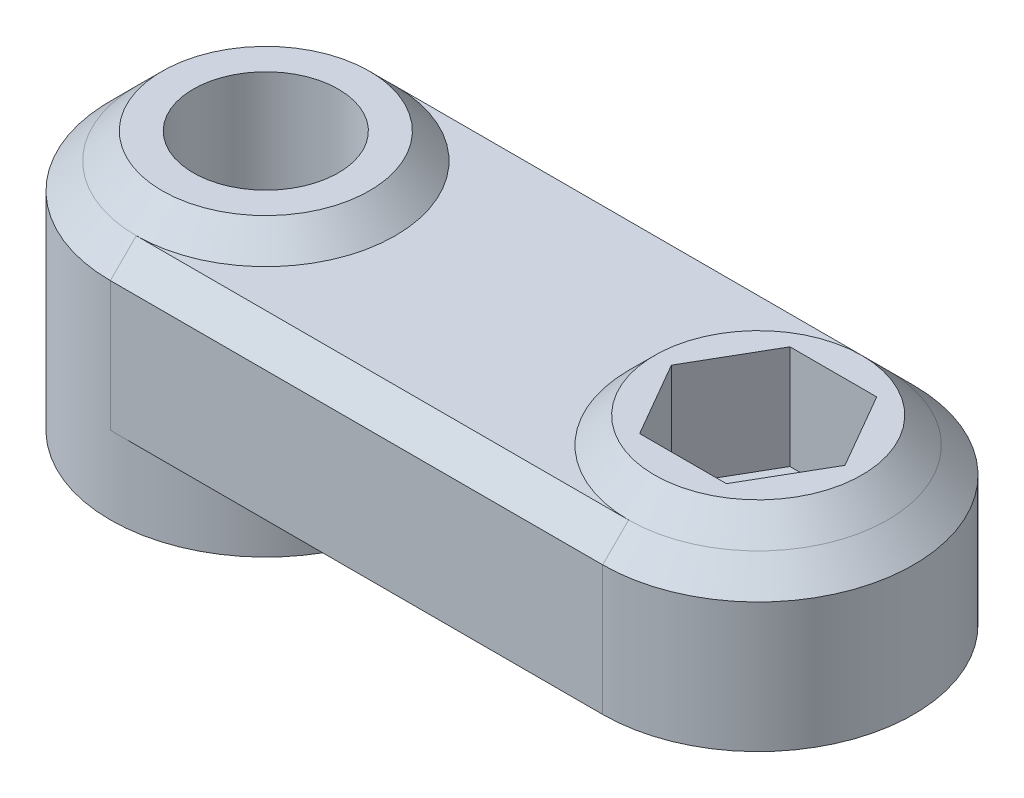
SolidWorks part; units mm, degrees
ref_plane "前视基准面" through (0, 0, 0) normal (0, 0, 1) x (1, 0, 0)
ref_plane "上视基准面" through (0, 0, 0) normal (0, 1, 0) x (1, 0, 0)
ref_plane "右视基准面" through (0, 0, 0) normal (1, 0, 0) x (0, 0, -1)
sketch "草图1" plane through (0, 0, 0) normal (0, 1, 0) x (1, 0, 0)
  line L0 (0, 0) -> (19, 0) construction
  line L1 (0, 6) -> (19, 6)
  line L2 (0, -6) -> (19, -6)
  arc A0 (0, 6) -> (0, -6) centre (0, 0) ccw
  arc A1 (19, -6) -> (19, 6) centre (19, 0) ccw
  point P3 (9.5, 0)
  dimension "D1" = 19
  dimension "D2" = 12
extrude "凸台-拉伸1" add sketch "草图1" along normal blind 10
sketch "草图2" plane through (0, 0, 0) normal (0, 0, 1) x (1, 0, 0)
  line L0 (0, -1.4276) -> (0, 12.6969) construction
  line L1 (0, 10) -> (-2.8, 10)
  line L2 (0, 10) -> (-6, 10) construction
  line L3 (-2.8, 10) -> (-2.8, 5)
  line L4 (-2.8, 5) -> (-1.85, 5)
  line L5 (-1.85, 5) -> (-1.85, 2)
  line L6 (-1.85, 2) -> (-2.8, 2)
  line L7 (-2.8, 2) -> (-2.8, 0)
  line L8 (-6, 0) -> (0, 0) construction
  line L9 (-2.8, 0) -> (0, 0)
  line L10 (0, 10) -> (0, 0)
  dimension "D1" = 5.6
  dimension "D2" = 5
  dimension "D3" = 3.7
  dimension "D4" = 3
revolve "切除-旋转1" cut sketch "草图2" angle 360 about L0
sketch "草图3" plane through (0, 0, 0) normal (0, 0, 1) x (1, 0, 0)
  line L0 (19, 0) -> (19, 10) construction
  line L1 (19, 0) -> (16.675, 0)
  line L2 (0, 0) -> (19, 0) construction
  line L3 (16.675, 0) -> (16.675, 6)
  line L4 (16.675, 6) -> (16.25, 6)
  line L5 (16.25, 6) -> (16.25, 10)
  line L6 (0, 10) -> (19, 10) construction
  line L7 (16.25, 10) -> (19, 10)
  line L8 (19, 0) -> (19, 10)
  dimension "D1" = 4.65
  dimension "D2" = 6
  dimension "D3" = 5.5
revolve "切除-旋转2" cut sketch "草图3" angle 360 about L0
chamfer "倒角1" distance 2 angle 45 4 edges at (9.5, 10, -6) (-6, 10, 0) (25, 10, 0) (9.5, 10, 6)
sketch "草图4" plane through (0, 0, 0) normal (0, -1, 0) x (1, 0, 0)
  line L0 (0, 6) -> (19, 6) construction
  line L1 (2.1073, 3.65) -> (-2.1073, 3.65)
  line L2 (-2.1073, 3.65) -> (-4.2147, 0)
  line L3 (-4.2147, 0) -> (-2.1073, -3.65)
  line L4 (-2.1073, -3.65) -> (2.1073, -3.65)
  line L5 (2.1073, -3.65) -> (4.2147, 0)
  line L6 (4.2147, 0) -> (2.1073, 3.65)
  circle A0 centre (0, 0) radius 3.65 construction
  dimension "D1" = 7.3
extrude "切除-拉伸1" cut sketch "草图4" against normal blind 5
sketch "草图5" plane through (0, 0, 0) normal (0, -1, 0) x (1, 0, 0)
  circle A0 centre (0, 0) radius 6
  circle A1 centre (0, 0) radius 32.436
  arc A2 (0, 6) -> (0, -6) centre (0, 0) ccw construction
extrude "切除-拉伸2" cut sketch "草图5" against normal blind 3
sketch "草图6" plane through (0, 10, 0) normal (0, 1, 0) x (1, 0, 0)
  line L0 (19, 4) -> (0, 4) construction
  line L1 (20.6743, 2.9) -> (17.3257, 2.9)
  line L2 (17.3257, 2.9) -> (15.6514, 0)
  line L3 (15.6514, 0) -> (17.3257, -2.9)
  line L4 (17.3257, -2.9) -> (20.6743, -2.9)
  line L5 (20.6743, -2.9) -> (22.3486, 0)
  line L6 (22.3486, 0) -> (20.6743, 2.9)
  circle A0 centre (19, 0) radius 2.9 construction
  dimension "D1" = 5.8
extrude "切除-拉伸3" cut sketch "草图6" against normal blind 4
sketch "草图7" plane through (0, 10, 0) normal (0, 1, 0) x (1, 0, 0)
  line L1 (33.7128, -22.6227) -> (-20.3488, -22.6227)
  line L2 (33.7128, -22.6227) -> (33.7128, 24.9049)
  line L3 (33.7128, 24.9049) -> (-20.3488, 24.9049)
  line L4 (-20.3488, -22.6227) -> (-20.3488, 24.9049)
  circle A0 centre (0, 0) radius 4
  circle A1 centre (19, 0) radius 4
extrude "切除-拉伸4" cut sketch "草图7" against normal blind 1
chamfer "倒角2" distance 1 angle 45 2 edges at (19, 9, 4) (0, 9, 4)
